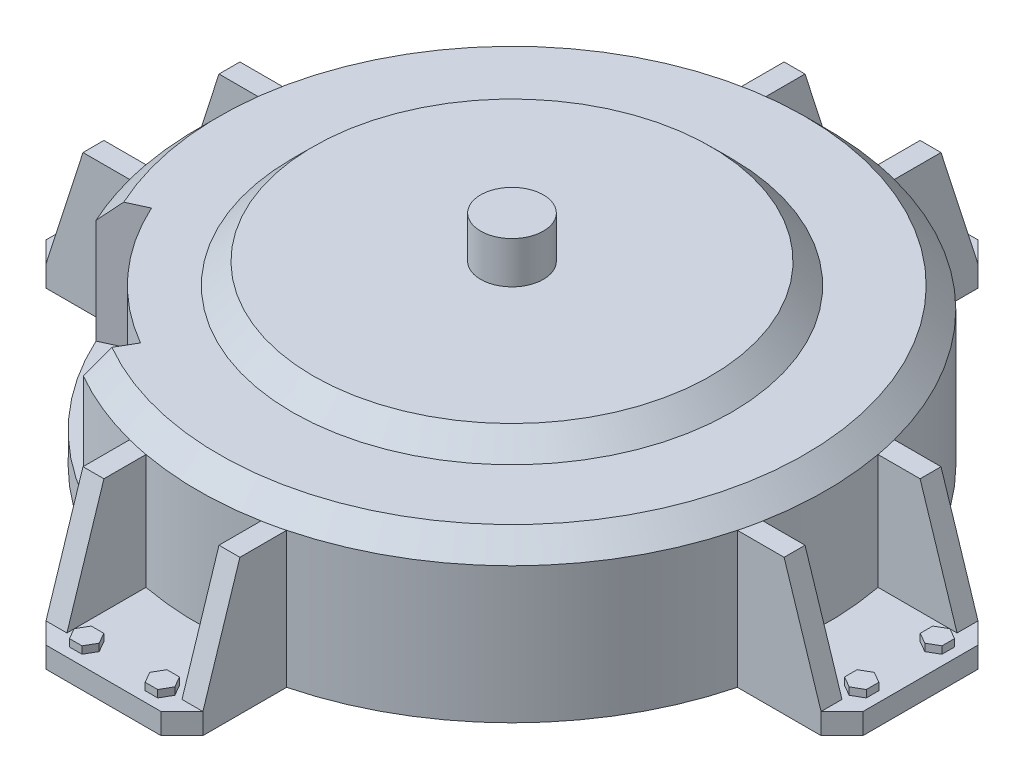
SolidWorks part; units mm, degrees
ref_plane "Front Plane" through (0, 0, 0) normal (0, 0, 1) x (1, 0, 0)
ref_plane "Top Plane" through (0, 0, 0) normal (0, 1, 0) x (1, 0, 0)
ref_plane "Right Plane" through (0, 0, 0) normal (1, 0, 0) x (0, 0, -1)
sketch "Sketch1" plane through (0, 0, 0) normal (0, 1, 0) x (1, 0, 0)
  circle A0 centre (0, 0) radius 150
  dimension "D1" = 300
extrude "Boss-Extrude1" add sketch "Sketch1" along normal blind 75
chamfer "Chamfer1" distance 10 angle 45 1 edges at (0, 75, 150)
sketch "Sketch2" plane through (0, 0, 0) normal (0, -1, 0) x (1, 0, 0)
  line L1 (-145.2369, 37.5) -> (-195.2369, 37.5)
  line L3 (-145.2369, -37.5) -> (-195.2369, -37.5)
  line L4 (-195.2369, 37.5) -> (-195.2369, -37.5)
  line L5 (-150, 0) -> (-195.2369, -37.5) construction
  line L6 (-150, 0) -> (-195.2369, 37.5) construction
  circle A0 centre (0, 0) radius 150 construction
  arc A1 (-145.2369, 37.5) -> (-145.2369, -37.5) centre (0, 0) ccw
  point P0 (-150, 0)
  dimension "D1" = 75
  dimension "D2" = 50
extrude "Boss-Extrude2" add sketch "Sketch2" against normal blind 10
chamfer "Chamfer2" distance 10 angle 45 2 edges at (-195.2369, 5, -37.5) (-195.2369, 5, 37.5)
sketch "Sketch3" plane through (0, 0, 37.5) normal (0, 0, 1) x (1, 0, 0)
  line L0 (-145.2369, 10) -> (-145.2369, 65)
  line L1 (-150, 65) -> (150, 65) construction
  line L2 (-145.2369, 65) -> (-167.5569, 65)
  line L3 (-167.5569, 65) -> (-185.2369, 10)
  line L4 (-185.2369, 10) -> (-145.2369, 10)
  line L5 (-185.2369, 10) -> (-185.2369, 0) construction
  line L6 (-145.2369, 10) -> (-185.2369, 10) construction
  dimension "D1" = 17.68
extrude "Boss-Extrude3" add sketch "Sketch3" against normal blind 10
sketch "Sketch4" plane through (0, 10, 0) normal (0, 1, 0) x (1, 0, 0)
  line L0 (-185.2369, 37.5) -> (-185.2369, -73.6602) construction
  line L2 (-185.2369, -24.0801) -> (-180.0407, -21.0801)
  line L3 (-180.0407, -21.0801) -> (-180.0407, -15.0801)
  line L4 (-180.0407, -15.0801) -> (-185.2369, -12.0801)
  line L5 (-185.2369, -12.0801) -> (-190.433, -15.0801)
  line L6 (-190.433, -15.0801) -> (-190.433, -21.0801)
  line L7 (-190.433, -21.0801) -> (-185.2369, -24.0801)
  circle A0 centre (-185.2369, -18.0801) radius 5.1962 construction
  dimension "D1" = 6
extrude "Boss-Extrude4" add sketch "Sketch4" along normal blind 3.5
mirror "Mirror1" about plane through (0, 0, 0) normal (0, 0, 1) of "Boss-Extrude3", "Boss-Extrude4"
pattern_circular "CirPattern1" count 4 over 360 about axis through (0, 0, 0) along (0, 1, 0) of "Boss-Extrude2", "Boss-Extrude3", "Boss-Extrude4", "Mirror1", "Chamfer2"
sketch "Sketch5" plane through (0, 75, 0) normal (0, 1, 0) x (1, 0, 0)
  line L2 (-118.1912, -54.1371) -> (-136.3745, -62.4659)
  line L3 (-65, -112.5833) -> (-75, -129.9038)
  arc A0 (-118.1912, -54.1371) -> (-65, -112.5833) centre (0, 0) ccw
  arc A1 (-145.2369, -37.5) -> (-37.5, -145.2369) centre (0, 0) ccw construction
  arc A2 (-136.3745, -62.4659) -> (-75, -129.9038) centre (0, 0) ccw
  dimension "D3" = 260
extrude "Cut-Extrude1" cut sketch "Sketch5" against normal blind 60
sketch "Sketch6" plane through (0, 75, 0) normal (0, 1, 0) x (1, 0, 0)
  circle A0 centre (0, 0) radius 110
  dimension "D1" = 220
extrude "Boss-Extrude5" add sketch "Sketch6" along normal blind 10
chamfer "Chamfer3" distance 15 angle 45 1 edges at (0, 85, 110)
sketch "Sketch7" plane through (0, 85, 0) normal (0, 1, 0) x (1, 0, 0)
  circle A0 centre (0, 0) radius 15
  dimension "D1" = 30
extrude "Boss-Extrude6" add sketch "Sketch7" along normal blind 20
